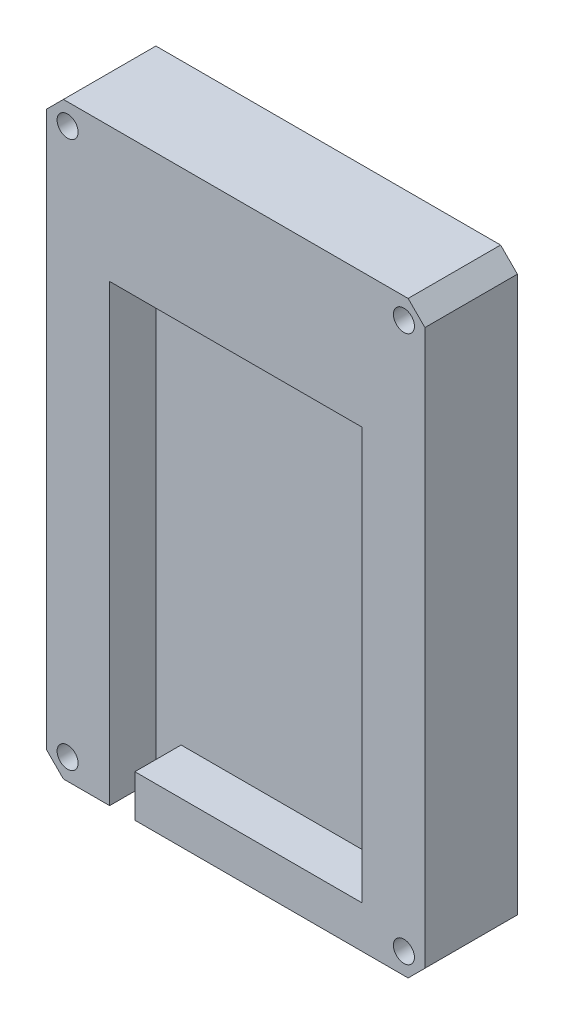
SolidWorks part; units mm, degrees
ref_plane "Front Plane" through (0, 0, 0) normal (0, 0, 1) x (1, 0, 0)
ref_plane "Top Plane" through (0, 0, 0) normal (0, 1, 0) x (1, 0, 0)
ref_plane "Right Plane" through (0, 0, 0) normal (1, 0, 0) x (0, 0, -1)
sketch "Sketch1" plane through (0, 0, 0) normal (0, 0, 1) x (1, 0, 0)
  line L0 (22.5, -29.5) -> (22.5, 40.5)
  line L1 (-15, -24.5) -> (15, -24.5)
  line L2 (-15, -24.5) -> (-15, 24.5)
  line L3 (-15, 24.5) -> (15, 24.5)
  line L4 (15, -24.5) -> (15, 24.5)
  line L5 (-15, -24.5) -> (15, 24.5) construction
  line L6 (-15, 24.5) -> (15, -24.5) construction
  line L7 (-22.5, 40.5) -> (22.5, 40.5)
  line L8 (-22.5, -29.5) -> (-22.5, 40.5)
  line L9 (-22.5, -29.5) -> (22.5, -29.5)
  line L10 (-15, -24.5) -> (-15, -29.5)
  line L11 (-12, -24.5) -> (-12, -29.5)
  line L13 (-20, -27) -> (-20, 38) construction
  line L14 (-20, 38) -> (20, 38) construction
  line L15 (20, -27) -> (20, 38) construction
  line L16 (-20, -27) -> (20, -27) construction
  point P0 (0, 0)
  dimension "D1" = 49
  dimension "D2" = 30
  dimension "D4" = 3
  dimension "D3" = 65
  dimension "D5" = 40
  dimension "D6" = 5
  dimension "D7" = 45
  dimension "D8" = 45
  dimension "D9" = 70
  dimension "D10" = 40
  dimension "D11" = 65
  dimension "D12" = 90
  dimension "D13" = 2.5
  dimension "D14" = 90
  dimension "D15" = 22.5
  dimension "D16" = 20
  dimension "D17" = 22.5
extrude "Boss-Extrude1" add sketch "Sketch1" along normal blind 5.5 contours L1 L9 L0 L7 L8 L2 L3 L4 region at (5.25, -28.6678, 0)
extrude "Boss-Extrude2" add sketch "Sketch1<3>" against normal blind 5.5 contours L1 L9 L0 L7 L8 L2 L3 L4 | L1 L4 L3 L2 | L1 L9 region at (5.25, -28.6678, 0) region at (-13.5, -27, 0) region at (0, 0, 0)
sketch "Sketch1<3>" plane through (0, 0, 0) normal (0, 0, 1) x (1, 0, 0) same geometry as "Sketch1"
sketch "Sketch2" plane through (0, 0, -5.5) normal (0, 0, -1) x (-1, 0, 0)
  point P0 (20, 38)
  point P3 (-20, 38)
  point P6 (-20, -27)
  point P9 (20, -27)
hole_wizard "Tap Drill for M3 Tap1" positions "Sketch2" profile "Sketch3" hole size "M3" standard "ISO" end condition through all
sketch "Sketch3" plane through (-20, 38, -5.5) normal (1, 0, 0) x (0, 1, 0)
  line L0 (0, 0) -> (0, 11)
  line L1 (0, 11) -> (1.25, 11)
  line L2 (1.25, 11) -> (1.25, 0.025)
  line L3 (1.25, 0.025) -> (1.275, 0)
  line L5 (1.275, 0) -> (0, 0)
  line L6 (-1.25, 0.025) -> (-1.275, 0) construction
  line L11 (0, -6.35) -> (0, 107.95) construction
  dimension "Thru Hole Dia." = 2.5
  dimension "Thru Hole Depth" = 11
  dimension "Near C'Sink Dia." = 2.55
  dimension "Near C'Sink Angle" = 90
chamfer "Chamfer1" distance 2 angle 45 4 edges at (22.5, -29.5, 0) (22.5, 40.5, 0) (-22.5, 40.5, 0) (-22.5, -29.5, 0)
